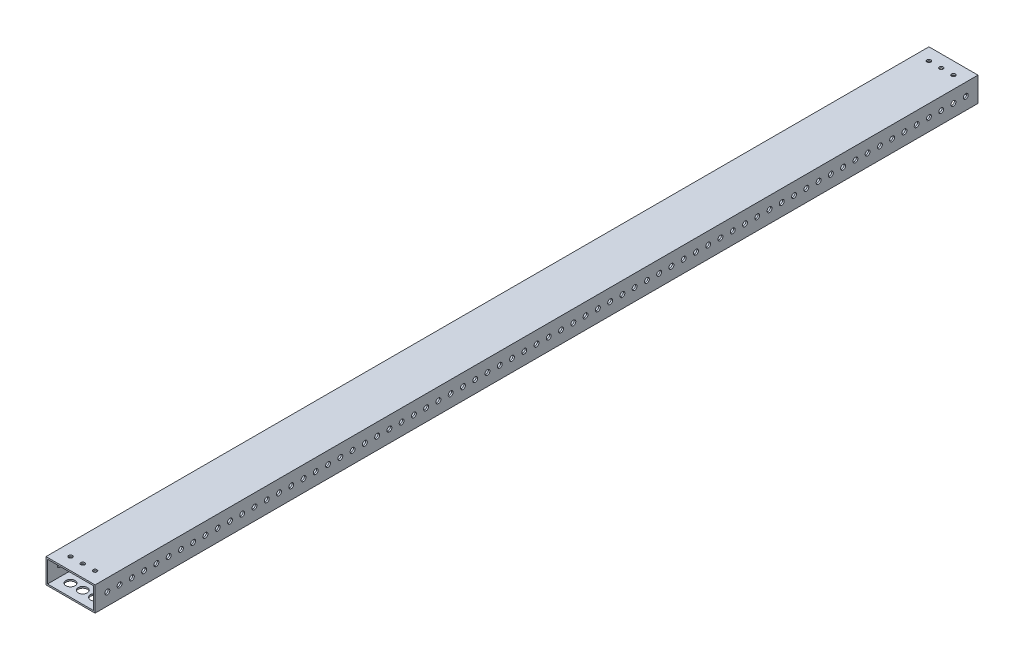
SolidWorks part; units mm, degrees
other "Markup1"
sketch "Sketch5" plane through (-25.4, -12.7, -457.2) normal (-0.35, -0.9329, -0.0852) x (-0.8023, 0.2515, 0.5413)
ref_plane "Front Plane" through (0, 0, 0) normal (0, 0, 1) x (1, 0, 0)
ref_plane "Top Plane" through (0, 0, 0) normal (0, 1, 0) x (1, 0, 0)
ref_plane "Right Plane" through (0, 0, 0) normal (1, 0, 0) x (0, 0, -1)
sketch "Sketch1" plane through (0, 0, 0) normal (0, 0, 1) x (1, 0, 0)
  line L0 (-23.8125, 11.1125) -> (23.8125, 11.1125)
  line L1 (-25.4, -12.7) -> (25.4, -12.7)
  line L2 (-25.4, -12.7) -> (-25.4, 12.7)
  line L3 (-25.4, 12.7) -> (25.4, 12.7)
  line L4 (25.4, -12.7) -> (25.4, 12.7)
  line L5 (-25.4, -12.7) -> (25.4, 12.7) construction
  line L6 (-25.4, 12.7) -> (25.4, -12.7) construction
  line L7 (23.8125, -11.1125) -> (23.8125, 11.1125)
  line L8 (-23.8125, -11.1125) -> (23.8125, -11.1125)
  line L9 (-23.8125, -11.1125) -> (-23.8125, 11.1125)
  point P0 (0, 0)
  dimension "D1" = 50.8
  dimension "D2" = 25.4
  dimension "D3" = 1.5875
extrude "Boss-Extrude1" add sketch "Sketch1" along normal mid plane 914.4
sketch "Sketch2" plane through (25.4, 0, 0) normal (1, 0, 0) x (0, 0, -1)
  line L0 (-457.2, 12.7) -> (457.2, 12.7) construction
  line L1 (457.2, -12.7) -> (457.2, 12.7) construction
  line L2 (-457.2, -12.7) -> (-457.2, 12.7) construction
  circle A0 centre (444.5, 0) radius 2.54
  circle A1 centre (431.8, 0) radius 2.54
  circle A2 centre (419.1, 0) radius 2.54
  circle A3 centre (406.4, 0) radius 2.54
  circle A4 centre (393.7, 0) radius 2.54
  circle A5 centre (381, 0) radius 2.54
  circle A6 centre (368.3, 0) radius 2.54
  circle A7 centre (355.6, 0) radius 2.54
  circle A8 centre (342.9, 0) radius 2.54
  circle A9 centre (330.2, 0) radius 2.54
  circle A10 centre (317.5, 0) radius 2.54
  circle A11 centre (304.8, 0) radius 2.54
  circle A12 centre (292.1, 0) radius 2.54
  circle A13 centre (279.4, 0) radius 2.54
  circle A14 centre (266.7, 0) radius 2.54
  circle A15 centre (254, 0) radius 2.54
  circle A16 centre (241.3, 0) radius 2.54
  circle A17 centre (228.6, 0) radius 2.54
  circle A18 centre (215.9, 0) radius 2.54
  circle A19 centre (203.2, 0) radius 2.54
  circle A20 centre (190.5, 0) radius 2.54
  circle A21 centre (177.8, 0) radius 2.54
  circle A22 centre (165.1, 0) radius 2.54
  circle A23 centre (152.4, 0) radius 2.54
  circle A24 centre (139.7, 0) radius 2.54
  circle A25 centre (127, 0) radius 2.54
  circle A26 centre (114.3, 0) radius 2.54
  circle A27 centre (101.6, 0) radius 2.54
  circle A28 centre (88.9, 0) radius 2.54
  circle A29 centre (76.2, 0) radius 2.54
  circle A30 centre (63.5, 0) radius 2.54
  circle A31 centre (50.8, 0) radius 2.54
  circle A32 centre (38.1, 0) radius 2.54
  circle A33 centre (25.4, 0) radius 2.54
  circle A34 centre (12.7, 0) radius 2.54
  circle A35 centre (0, 0) radius 2.54
  circle A36 centre (-12.7, 0) radius 2.54
  circle A37 centre (-25.4, 0) radius 2.54
  circle A38 centre (-38.1, 0) radius 2.54
  circle A39 centre (-50.8, 0) radius 2.54
  circle A40 centre (-63.5, 0) radius 2.54
  circle A41 centre (-76.2, 0) radius 2.54
  circle A42 centre (-88.9, 0) radius 2.54
  circle A43 centre (-101.6, 0) radius 2.54
  circle A44 centre (-114.3, 0) radius 2.54
  circle A45 centre (-127, 0) radius 2.54
  circle A46 centre (-139.7, 0) radius 2.54
  circle A47 centre (-152.4, 0) radius 2.54
  circle A48 centre (-165.1, 0) radius 2.54
  circle A49 centre (-177.8, 0) radius 2.54
  circle A50 centre (-190.5, 0) radius 2.54
  circle A51 centre (-203.2, 0) radius 2.54
  circle A52 centre (-215.9, 0) radius 2.54
  circle A53 centre (-228.6, 0) radius 2.54
  circle A54 centre (-241.3, 0) radius 2.54
  circle A55 centre (-254, 0) radius 2.54
  circle A56 centre (-266.7, 0) radius 2.54
  circle A57 centre (-279.4, 0) radius 2.54
  circle A58 centre (-292.1, 0) radius 2.54
  circle A59 centre (-304.8, 0) radius 2.54
  circle A60 centre (-317.5, 0) radius 2.54
  circle A61 centre (-330.2, 0) radius 2.54
  circle A62 centre (-342.9, 0) radius 2.54
  circle A63 centre (-355.6, 0) radius 2.54
  circle A64 centre (-368.3, 0) radius 2.54
  circle A65 centre (-381, 0) radius 2.54
  circle A66 centre (-393.7, 0) radius 2.54
  circle A67 centre (-406.4, 0) radius 2.54
  circle A68 centre (-419.1, 0) radius 2.54
  circle A69 centre (-431.8, 0) radius 2.54
  circle A70 centre (-444.5, 0) radius 2.54
  dimension "D1" = 5.08
  dimension "D2" = 12.7
  dimension "D3" = 12.7
  dimension "D5" = 12.7
  dimension "D6" = 12.7
  dimension "D4" = 71
extrude "Cut-Extrude1" cut sketch "Sketch2" against normal through all
sketch "Sketch3" plane through (0, 12.7, 0) normal (0, 1, 0) x (1, 0, 0)
  line L2 (25.4, -457.2) -> (-25.4, -457.2) construction
  line L3 (25.4, 0) -> (-25.4, 0) construction
  line L4 (25.4, -457.2) -> (25.4, 457.2) construction
  line L5 (-25.4, -457.2) -> (-25.4, 457.2) construction
  circle A0 centre (0, -444.5) radius 2.0193
  circle A1 centre (12.7, -444.5) radius 2.0193
  circle A2 centre (-12.7, -444.5) radius 2.0193
  circle A3 centre (12.7, 444.5) radius 2.0193
  circle A4 centre (0, 444.5) radius 2.0193
  circle A5 centre (-12.7, 444.5) radius 2.0193
  dimension "D1" = 4.0386
  dimension "D2" = 12.7
  dimension "D3" = 12.7
  dimension "D4" = 12.7
extrude "Cut-Extrude2" cut sketch "Sketch3" against normal up to surface (1.5875 mm away) up to face at (0, 11.1125, 0)
sketch "Sketch4" plane through (0, -12.7, 0) normal (0, -1, 0) x (1, 0, 0)
  circle A0 centre (-12.7, 444.5) radius 2.0193 construction
  circle A1 centre (0, 444.5) radius 2.0193 construction
  circle A2 centre (12.7, 444.5) radius 2.0193 construction
  circle A3 centre (-12.7, 444.5) radius 2.0193
  circle A4 centre (0, 444.5) radius 2.0193
  circle A5 centre (12.7, 444.5) radius 2.0193
  circle A6 centre (-12.7, -444.5) radius 2.0193 construction
  circle A7 centre (0, -444.5) radius 2.0193 construction
  circle A8 centre (12.7, -444.5) radius 2.0193 construction
  circle A9 centre (-12.7, -444.5) radius 2.0193
  circle A10 centre (0, -444.5) radius 2.0193
  circle A11 centre (12.7, -444.5) radius 2.0193
  circle A12 centre (-12.7, 444.5) radius 4.7625
  circle A13 centre (0, 444.5) radius 4.7625
  circle A14 centre (12.7, 444.5) radius 4.7625
  circle A15 centre (-12.7, -444.5) radius 4.7625
  circle A16 centre (0, -444.5) radius 4.7625
  circle A17 centre (12.7, -444.5) radius 4.7625
  dimension "D1" = 9.525
  dimension "D2" = 9.525
extrude "Cut-Extrude4" cut sketch "Sketch4" against normal up to surface (1.5875 mm away) contours A12 A3 | A13 A4 | A4 | A3 | A5 | A14 A5 | A11 | A17 A11 | A16 A10 | A10 | A15 A9 | A9 region at (-12.7, -12.7, 444.5) region at (0, -12.7, 444.5) region at (12.7, -12.7, 444.5) region at (-12.7, -12.7, -444.5) region at (0, -12.7, -444.5) region at (12.7, -12.7, -444.5) region at (-17.3278, -12.7, 444.5) region at (-4.6278, -12.7, 444.5) region at (8.0722, -12.7, 444.5) region at (-17.3278, -12.7, -444.5) region at (-4.6278, -12.7, -444.5) region at (8.0722, -12.7, -444.5) up to face at (0, -11.1125, 0)
